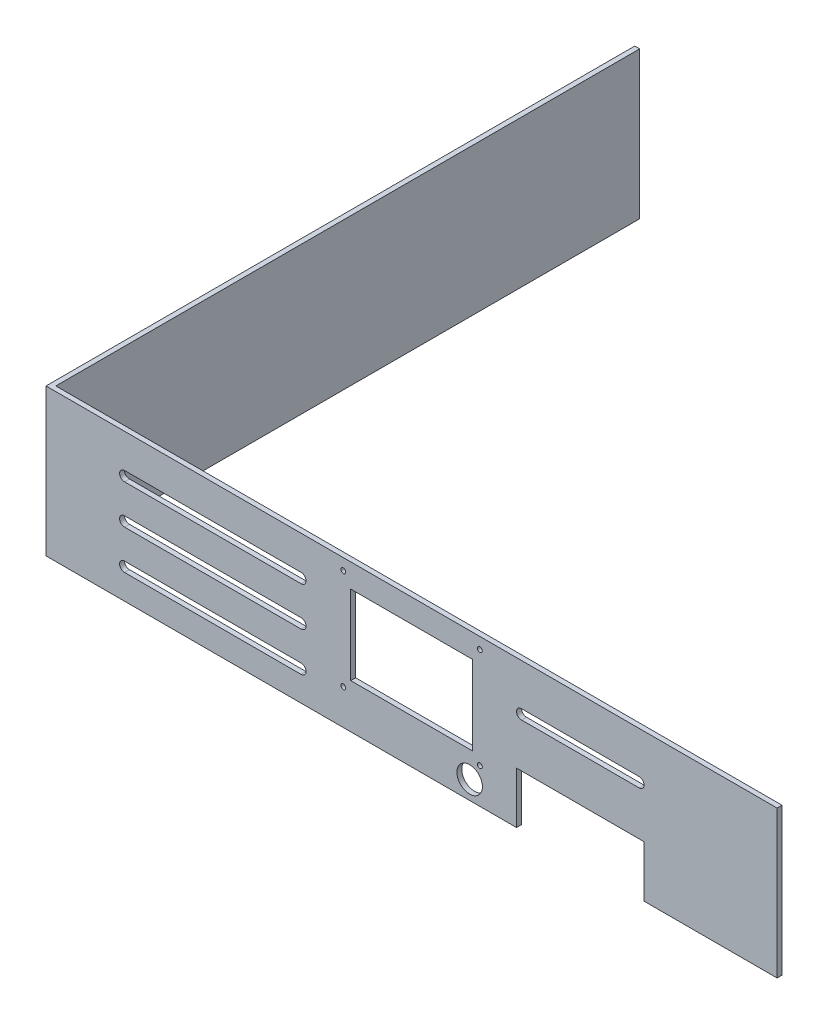
SolidWorks part; units mm, degrees
ref_plane "Front Plane" through (0, 0, 0) normal (0, 0, 1) x (1, 0, 0)
ref_plane "Top Plane" through (0, 0, 0) normal (0, 1, 0) x (1, 0, 0)
ref_plane "Right Plane" through (0, 0, 0) normal (1, 0, 0) x (0, 0, -1)
sketch "Sketch1" plane through (0, 0, 0) normal (0, 0, 1) x (1, 0, 0)
  line L1 (-236.5375, -47.625) -> (236.5375, -47.625)
  line L2 (-236.5375, -47.625) -> (-236.5375, 47.625)
  line L3 (-236.5375, 47.625) -> (236.5375, 47.625)
  line L4 (236.5375, -47.625) -> (236.5375, 47.625)
  line L5 (-236.5375, -47.625) -> (236.5375, 47.625) construction
  line L6 (-236.5375, 47.625) -> (236.5375, -47.625) construction
  point P0 (0, 0)
  dimension "D1" = 473.075
  dimension "D2" = 95.25
extrude "Boss-Extrude1" add sketch "Sketch1" along normal blind 3.175
sketch "Sketch3" plane through (0, 0, 3.175) normal (0, 0, 1) x (1, 0, 0)
  line L0 (0, -47.625) -> (0, -19.05)
  line L1 (-236.5375, -47.625) -> (236.5375, -47.625) construction
  line L3 (-39.37, -18.923) -> (39.37, -18.923)
  line L4 (-39.37, -18.923) -> (-39.37, 32.385)
  line L5 (-39.37, 32.385) -> (39.37, 32.385)
  line L6 (39.37, -18.923) -> (39.37, 32.385)
  dimension "D1" = 28.575
  dimension "D2" = 78.74
  dimension "D3" = 39.37
  dimension "D4" = 51.308
  dimension "D5" = 28.702
extrude "Cut-Extrude2" cut sketch "Sketch3" against normal through all contours L3 L6 L5 L4 region at (0, 6.731, 3.175)
sketch "Sketch4" plane through (0, 0, 3.175) normal (0, 0, 1) x (1, 0, 0)
  line L0 (-236.5375, -47.625) -> (236.5375, -47.625) construction
  line L1 (39.37, -18.923) -> (39.37, 32.385) construction
  circle A0 centre (37.592, -35.814) radius 8.255
  dimension "D1" = 16.51
  dimension "D2" = 11.811
  dimension "D3" = 1.778
extrude "Cut-Extrude3" cut sketch "Sketch4" against normal through all
sketch "Sketch5" plane through (0, 0, 3.175) normal (0, 0, 1) x (1, 0, 0)
  line L0 (39.37, -18.923) -> (39.37, 32.385) construction
  line L1 (-39.37, 32.385) -> (39.37, 32.385) construction
  line L2 (0, 0) -> (0, 11.1381)
  line L3 (0, 0) -> (6.9433, 0)
  circle A0 centre (44.196, 40.259) radius 1.5875
  circle A1 centre (44.196, -24.765) radius 1.5875
  circle A2 centre (-44.196, -24.765) radius 1.5875
  circle A3 centre (-44.196, 40.259) radius 1.5875
  dimension "D1" = 3.175
  dimension "D3" = 7.874
  dimension "D4" = 65.024
  dimension "D5" = 0
  dimension "D2" = 4.826
extrude "Cut-Extrude4" cut sketch "Sketch5" against normal through all contours A3 | A0 | A2 | A1 region at (44.196, 40.259, 3.175) region at (44.196, -24.765, 3.175) region at (-44.196, -24.765, 3.175) region at (-44.196, 40.259, 3.175)
sketch "Sketch6" plane through (0, 0, 0) normal (0, 0, -1) x (-1, 0, 0)
  line L0 (236.5375, -47.625) -> (-236.5375, -47.625) construction
  line L1 (236.5375, 47.625) -> (233.3625, 47.625)
  line L2 (236.5375, 47.625) -> (236.5375, -47.625)
  line L3 (236.5375, -47.625) -> (233.3625, -47.625)
  line L4 (233.3625, 47.625) -> (233.3625, -47.625)
  dimension "D1" = 3.175
extrude "Boss-Extrude2" add sketch "Sketch6" along normal blind 377.825
sketch "Sketch7" plane through (-236.5375, 0, 0) normal (-1, 0, 0) x (0, 0, 1)
  line L0 (3.175, 47.625) -> (-377.825, 47.625) construction
  line L1 (-339.725, 28.575) -> (-288.925, 28.575)
  line L2 (-339.725, 28.575) -> (-339.725, -44.45)
  line L3 (-339.725, -44.45) -> (-288.925, -44.45)
  line L4 (-288.925, 28.575) -> (-288.925, -44.45)
  line L5 (-377.825, -47.625) -> (-377.825, 47.625) construction
  line L6 (3.175, -47.625) -> (-377.825, -47.625) construction
  circle A0 centre (-254.127, -28.575) radius 3.81
  dimension "D5" = 123.698
  dimension "D6" = 19.05
  dimension "D1" = 19.05
  dimension "D2" = 50.8
  dimension "D3" = 38.1
  dimension "D4" = 3.175
sketch "Sketch8" plane through (0, 0, 3.175) normal (0, 0, 1) x (1, 0, 0)
  line L0 (-236.5375, -47.625) -> (-185.7375, -47.625)
  line L1 (-236.5375, -47.625) -> (236.5375, -47.625) construction
  line L5 (-185.7375, -28.3064) -> (-71.4375, -28.3064) construction
  line L6 (-185.7375, -25.1314) -> (-71.4375, -25.1314)
  line L7 (-185.7375, -31.4814) -> (-71.4375, -31.4814)
  line L8 (-185.7375, -2.9064) -> (-71.4375, -2.9064) construction
  line L9 (-185.7375, 0.2686) -> (-71.4375, 0.2686)
  line L10 (-185.7375, -6.0814) -> (-71.4375, -6.0814)
  line L11 (-185.7375, 22.4936) -> (-71.4375, 22.4936) construction
  line L12 (-185.7375, 25.6686) -> (-71.4375, 25.6686)
  line L13 (-185.7375, 19.3186) -> (-71.4375, 19.3186)
  line L15 (71.12, 17.4499) -> (147.32, 17.4499) construction
  line L16 (71.12, 20.6249) -> (147.32, 20.6249)
  line L17 (71.12, 14.2749) -> (147.32, 14.2749)
  line L20 (67.945, -14.3001) -> (150.495, -14.3001)
  line L21 (67.945, -14.3001) -> (67.945, -47.625)
  line L22 (67.945, -47.625) -> (150.495, -47.625)
  line L23 (150.495, -14.3001) -> (150.495, -47.625)
  arc A0 (-185.7375, -25.1314) -> (-185.7375, -31.4814) centre (-185.7375, -28.3064) ccw
  arc A1 (-71.4375, -31.4814) -> (-71.4375, -25.1314) centre (-71.4375, -28.3064) ccw
  arc A2 (-185.7375, 0.2686) -> (-185.7375, -6.0814) centre (-185.7375, -2.9064) ccw
  arc A3 (-71.4375, -6.0814) -> (-71.4375, 0.2686) centre (-71.4375, -2.9064) ccw
  arc A4 (-185.7375, 25.6686) -> (-185.7375, 19.3186) centre (-185.7375, 22.4936) ccw
  arc A5 (-71.4375, 19.3186) -> (-71.4375, 25.6686) centre (-71.4375, 22.4936) ccw
  arc A6 (71.12, 20.6249) -> (71.12, 14.2749) centre (71.12, 17.4499) ccw
  arc A7 (147.32, 14.2749) -> (147.32, 20.6249) centre (147.32, 17.4499) ccw
  point P5 (-128.5875, -28.3064)
  point P14 (-128.5875, -2.9064)
  point P20 (-128.5875, 22.4936)
  point P31 (109.22, 17.4499)
  line M17 (-236.5375, -47.625) -> (236.5375, -47.625)
extrude "Cut-Extrude6" cut sketch "Sketch8" against normal blind 29.464 contours L23 L20 L21 M17 | L17 A7 L16 A6 | L13 A5 L12 A4 | L10 A3 L9 A2 | L7 A1 L6 A0 region at (109.22, -30.9625, 3.175)
